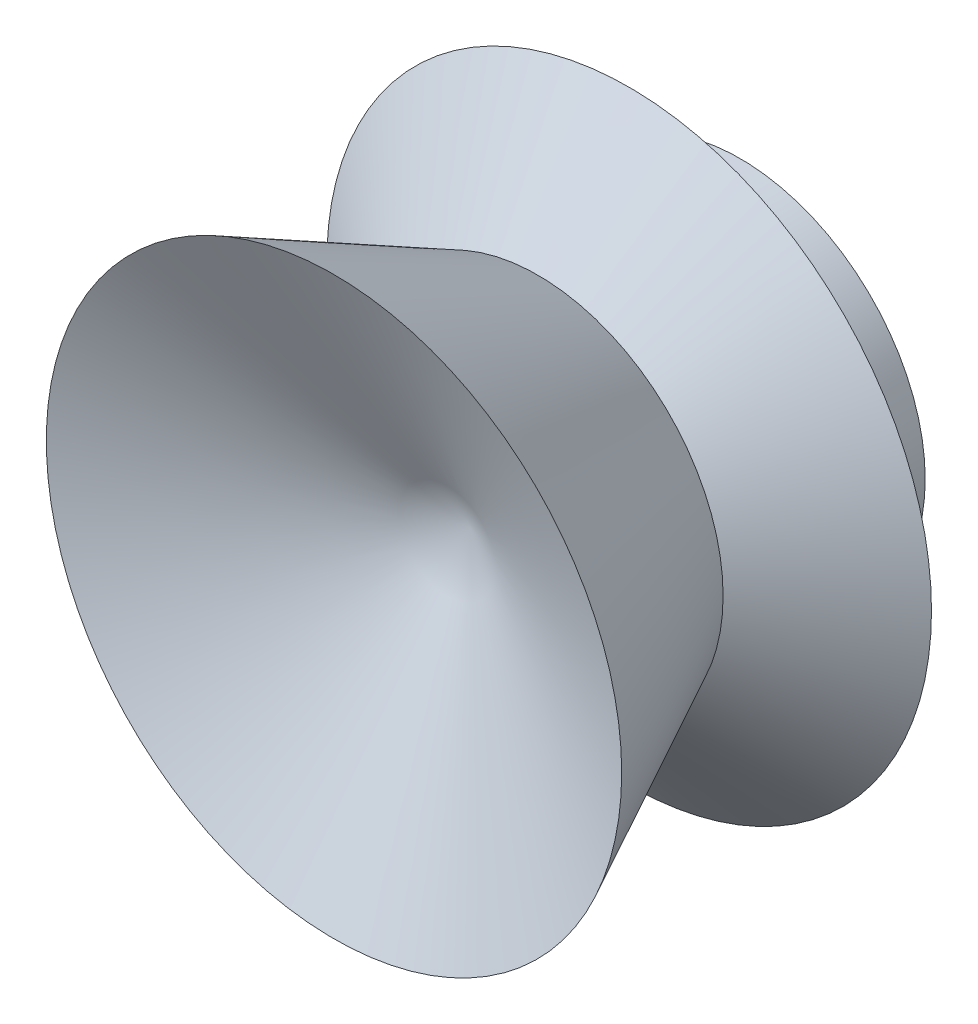
SolidWorks part; units mm, degrees
ref_plane "Front Plane" through (0, 0, 0) normal (0, 0, 1) x (1, 0, 0)
ref_plane "Top Plane" through (0, 0, 0) normal (0, 1, 0) x (1, 0, 0)
ref_plane "Right Plane" through (0, 0, 0) normal (1, 0, 0) x (0, 0, -1)
sketch "Sketch6" plane through (0, 0, 0) normal (0, 1, 0) x (1, 0, 0)
  line L0 (0, 0) -> (0, 50000) construction
  line L1 (0, 330.5889) -> (0, 104.8327)
  line L2 (0, 330.5889) -> (177.9177, 364.3515)
  line L3 (177.9177, 364.3515) -> (177.9177, 271.8099)
  line L4 (177.9177, 271.8099) -> (290.577, 257.7275)
  line L5 (290.577, 257.7275) -> (177.9177, 170.1036)
  line L6 (177.9177, 170.1036) -> (276.4946, -25.9326)
  line L7 (276.4946, -25.9326) -> (0, 104.8327)
revolve "Revolve1" add sketch "Sketch6" angle 360 about L0
scale "Scale1" scale about centroid uniform scaling yes scale factor 0.2
